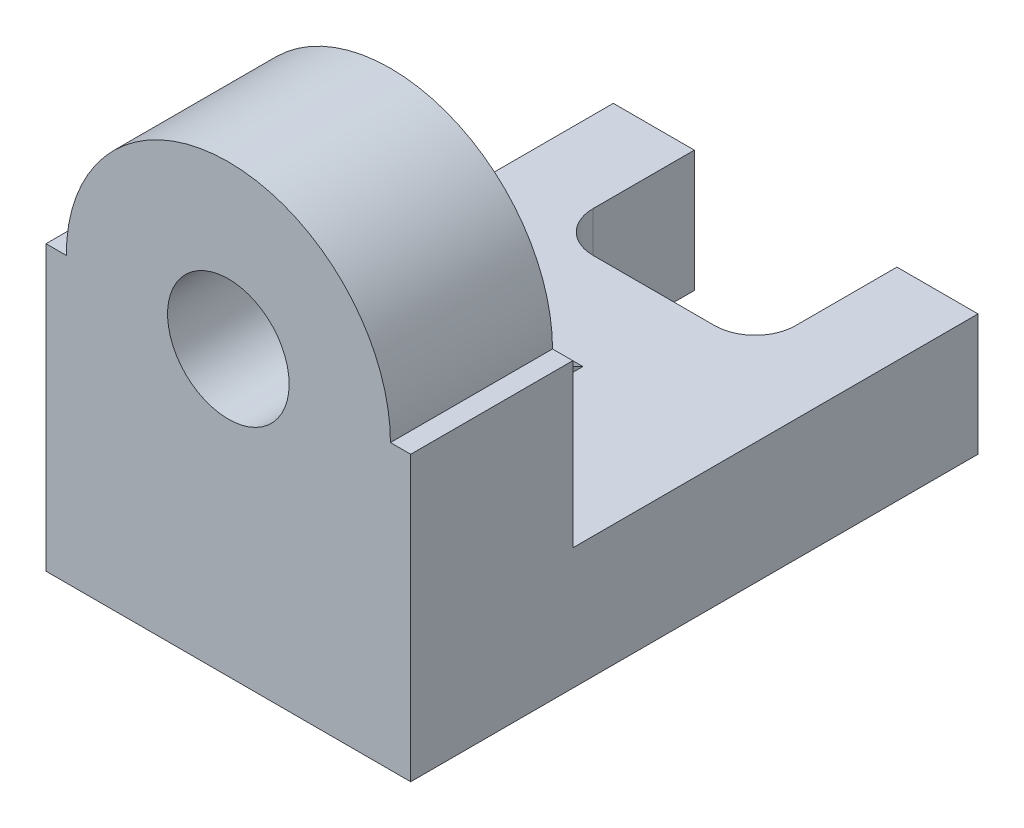
SolidWorks part; units mm, degrees
ref_plane "Front Plane" through (0, 0, 0) normal (0, 0, 1) x (1, 0, 0)
ref_plane "Top Plane" through (0, 0, 0) normal (0, 1, 0) x (1, 0, 0)
ref_plane "Right Plane" through (0, 0, 0) normal (1, 0, 0) x (0, 0, -1)
sketch "Sketch1" plane through (0, 0, 0) normal (0, 0, 1) x (1, 0, 0)
  line L0 (-40, 70) -> (-45, 70)
  line L1 (-45, 70) -> (-45, 0)
  line L2 (-45, 0) -> (45, 0)
  line L3 (45, 0) -> (45, 70)
  line L4 (45, 70) -> (40, 70)
  line L5 (0, 0) -> (0, 144.0252) construction
  arc A0 (-40, 70) -> (40, 70) centre (0, 70) cw
  circle A1 centre (0, 70) radius 15
  dimension "D2" = 40
  dimension "D4" = 30
  dimension "D1" = 90
  dimension "D3" = 70
extrude "Boss-Extrude1" add sketch "Sketch1" along normal blind 70 and the other way blind 70
sketch "Sketch2" plane through (-45, 0, 0) normal (-1, 0, 0) x (0, 0, 1)
  line L0 (70, 110) -> (-70, 110) construction
  line L1 (-70, 110) -> (30, 110)
  line L2 (-70, 110) -> (-70, 30)
  line L3 (-70, 30) -> (30, 30)
  line L4 (30, 110) -> (30, 30)
  line L5 (-70, 70) -> (-70, 0) construction
  line L6 (70, 70) -> (70, 0) construction
  line L7 (-70, 0) -> (70, 0) construction
  dimension "D1" = 40
  dimension "D2" = 30
extrude "Cut-Extrude1" cut sketch "Sketch2" against normal through all
sketch "Sketch3" plane through (0, 30, 0) normal (0, 1, 0) x (1, 0, 0)
  line L0 (45, 70) -> (-45, 70) construction
  line L1 (-25, 70) -> (25, 70)
  line L2 (-25, 70) -> (-25, 35)
  line L3 (-25, 35) -> (25, 35)
  line L4 (25, 70) -> (25, 35)
  line L5 (0, 0) -> (0, 83.3208) construction
  dimension "D1" = 50
  dimension "D2" = 35
extrude "Cut-Extrude2" cut sketch "Sketch3" against normal through all
fillet "Fillet1" radius 10 2 edges at (-25, 15, -35) (25, 15, -35)
sketch "Sketch4" plane through (0, 0, 0) normal (1, 0, 0) x (0, 0, -1)
  line L0 (-30, 50) -> (10, 30)
  line L1 (-30, 30) -> (-30, 70) construction
  line L2 (70, 30) -> (-30, 30) construction
  dimension "D1" = 40
  dimension "D2" = 20
rib "Rib1" sketch "Sketch4" sketch "Sketch4" thickness 15 extrusion direction parallel to sketch draft on no parameters "D1"=15
